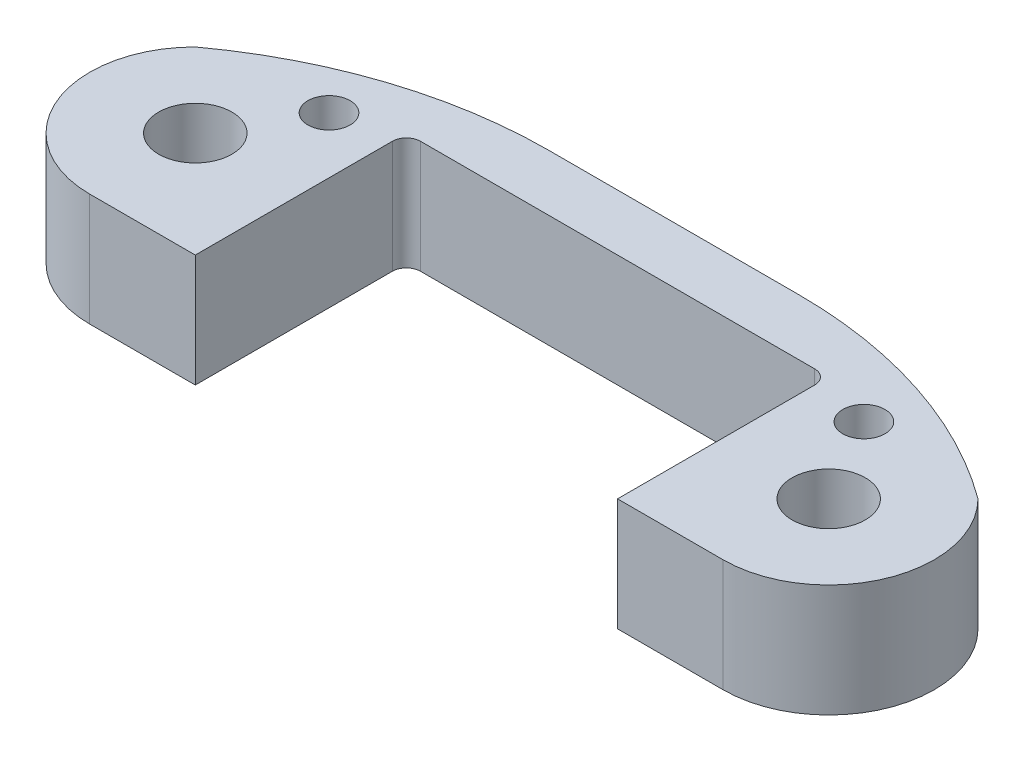
SolidWorks part; units mm, degrees
ref_plane "Plan de face" through (0, 0, 0) normal (0, 0, 1) x (1, 0, 0)
ref_plane "Plan de dessus" through (0, 0, 0) normal (0, 1, 0) x (1, 0, 0)
ref_plane "Plan de droite" through (0, 0, 0) normal (1, 0, 0) x (0, 0, -1)
sketch "Esquisse1" plane through (0, 0, 0) normal (0, 1, 0) x (1, 0, 0)
  line L0 (-30, 15) -> (-15, 0) construction
  line L1 (-30, 0) -> (-15, 0) construction
  line L2 (-30, 0) -> (-30, 15) construction
  line L3 (-30, 15) -> (-15, 15) construction
  line L4 (-15, 0) -> (-15, 15) construction
  line L5 (15, 0) -> (30, 0) construction
  line L6 (15, 0) -> (15, 15) construction
  line L7 (15, 15) -> (30, 15) construction
  line L8 (30, 0) -> (30, 15) construction
  line L9 (15, 0) -> (30, 15) construction
  line L10 (-15, 0) -> (15, 0) construction
  line L11 (-21.6066, 19) -> (21.6066, 19)
  line L12 (-14, 15) -> (14, 15)
  line L13 (0, 19) -> (0, 0) construction
  line L14 (-21.6066, 19) -> (-27.8033, 12.8033)
  line L15 (21.6066, 19) -> (27.8033, 12.8033)
  line L18 (-22.5, 0) -> (-15, 0)
  line L19 (15, 0) -> (22.5, 0)
  line L20 (-14, 15) -> (-15, 14)
  line L21 (-15, 14) -> (-15, 0)
  line L22 (14, 15) -> (15, 14)
  line L23 (15, 14) -> (15, 0)
  line L24 (-15, 14) -> (15, 14) construction
  circle A0 centre (-22.5, 7.5) radius 7.5 construction
  circle A1 centre (22.5, 7.5) radius 7.5 construction
  circle A2 centre (-22.5, 7.5) radius 1.1
  circle A3 centre (22.5, 7.5) radius 1.1
  arc A4 (-27.8033, 12.8033) -> (-22.5, 0) centre (-22.5, 7.5) ccw
  arc A5 (27.8033, 12.8033) -> (22.5, 0) centre (22.5, 7.5) cw
  point P8 (0, 0)
  point P21 (0, 15)
  point P28 (15, 14)
  dimension "D3" = 2.2
  dimension "D1" = 30
  dimension "D2" = 15
  dimension "D4" = 4
  dimension "D5" = 1
  dimension "D6" = 28
extrude "Boss.-Extru.1" add sketch "Esquisse1" along normal blind 8
sketch "Esquisse2" plane through (0, 8, 0) normal (0, 1, 0) x (1, 0, 0)
  circle A0 centre (-22.5, 7.5) radius 2.6
  circle A1 centre (22.5, 7.5) radius 2.6
  dimension "D1" = 5.2
extrude "Enlèv. mat.-Extru.1" cut sketch "Esquisse2" against normal offset from surface (6 mm away) 2 up to face at (0, 0, -9.8386)
chamfer "Chanfrein1" distance 2 angle 45 2 edges at (22.5, 0, -6.4) (-22.5, 0, -6.4)
sketch "Esquisse4" plane through (0, 0, 0) normal (0, -1, 0) x (1, 0, 0)
  line L0 (19, -13.5) -> (-19, -13.5) construction
  line L1 (0, -13.5) -> (0, 0) construction
  circle A0 centre (19, -13.5) radius 1.5
  circle A1 centre (-19, -13.5) radius 1.5
  dimension "D3" = 3
  dimension "D1" = 13.5
  dimension "D2" = 38
extrude "Enlèv. mat.-Extru.2" cut sketch "Esquisse4" against normal up to surface (8 mm away) up to face at (-22.5, 8, -4.9)
sketch "Esquisse5" plane through (0, 8, 0) normal (0, 1, 0) x (1, 0, 0)
  line L0 (15, 14) -> (14, 14)
  line L1 (14, 14) -> (14, 15)
  line L2 (0, 0) -> (0, 19) construction
  line L3 (-22.5, 0) -> (22.5, 0) construction
  line L4 (21.6066, 19) -> (-21.6066, 19) construction
  line L5 (-14, 14) -> (-14, 15)
  line L6 (-15, 14) -> (-14, 14)
  arc A0 (15, 14) -> (14, 15) centre (14, 14) ccw
  arc A1 (-15, 14) -> (-14, 15) centre (-14, 14) cw
extrude "Enlèv. mat.-Extru.3" cut sketch "Esquisse5" against normal through all
fillet "Congé1" radius 32 2 edges at (21.6066, 4, -19) (-21.6066, 4, -19)
